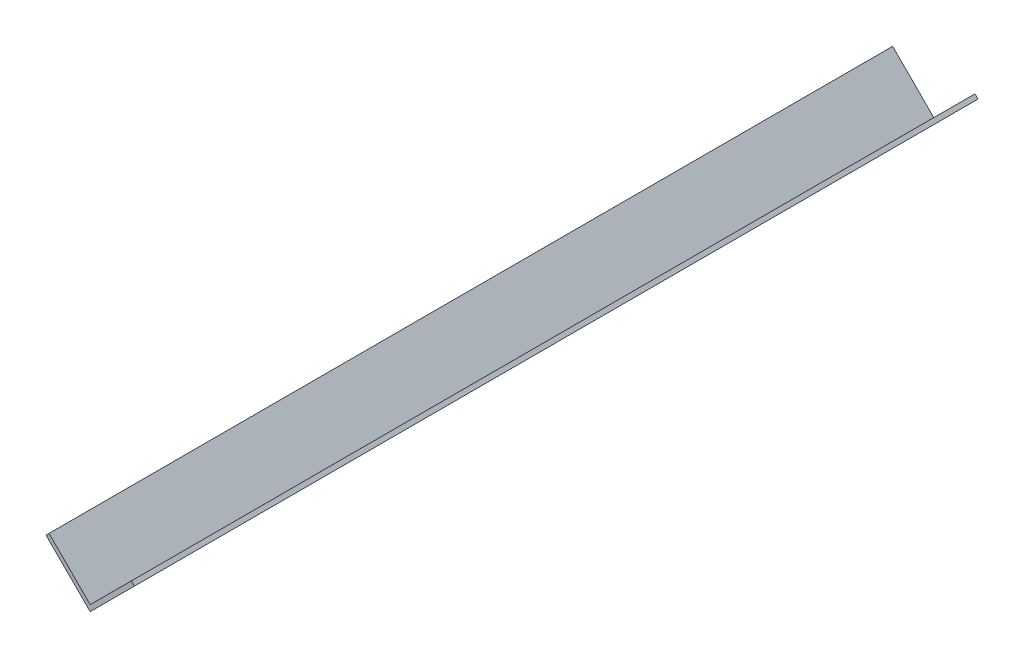
SolidWorks part; units mm, degrees
material "6061 Alloy"
ref_plane "Front Plane" through (0, 0, 0) normal (0, 0, 1) x (1, 0, 0)
ref_plane "Top Plane" through (0, 0, 0) normal (0, 1, 0) x (1, 0, 0)
ref_plane "Right Plane" through (0, 0, 0) normal (1, 0, 0) x (0, 0, -1)
sketch "Sketch1" plane through (0, 0, 0) normal (0, 0, 1) x (1, 0, 0)
  line L0 (0, 0) -> (-17.9605, 17.9605)
  line L1 (-17.9605, 17.9605) -> (-16.7257, 19.1953)
  line L2 (-16.7257, 19.1953) -> (0, 2.4696)
  line L3 (0, 2.4696) -> (16.7257, 19.1953)
  line L4 (16.7257, 19.1953) -> (17.9605, 17.9605)
  line L5 (17.9605, 17.9605) -> (0, 0)
  dimension "D1" = 1.7463
  dimension "D2" = 25.4
extrude "Boss-Extrude1" add sketch "Sketch1" along normal blind 342.9
